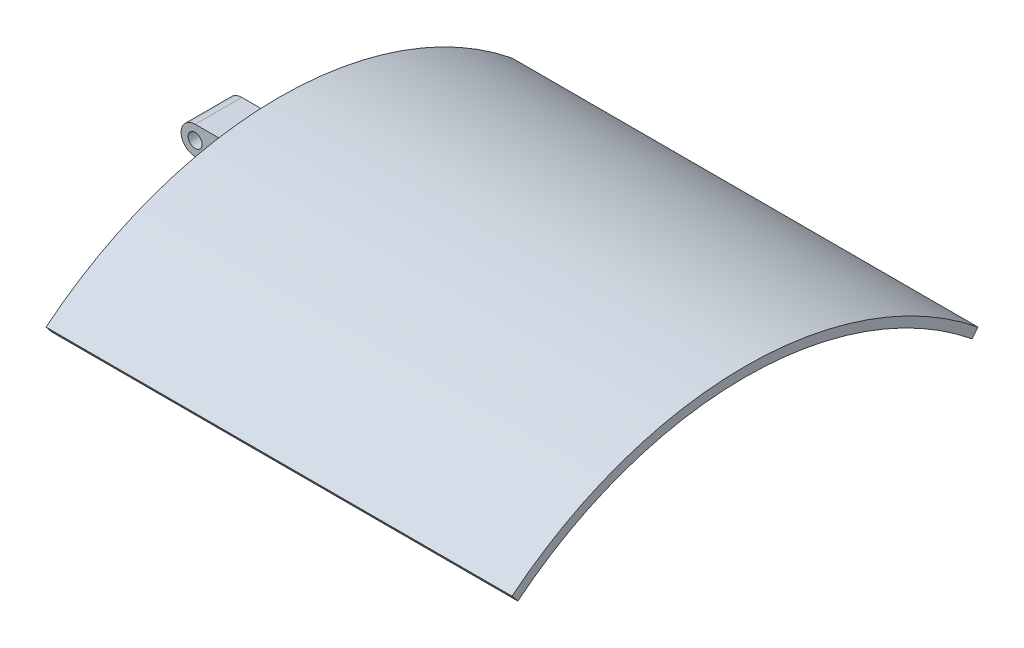
SolidWorks part; units mm, degrees
ref_plane "Plan de face" through (0, 0, 0) normal (0, 0, 1) x (1, 0, 0)
ref_plane "Plan de dessus" through (0, 0, 0) normal (0, 1, 0) x (1, 0, 0)
ref_plane "Plan de droite" through (0, 0, 0) normal (1, 0, 0) x (0, 0, -1)
sketch "Esquisse1" plane through (0, 0, 0) normal (1, 0, 0) x (0, 0, -1)
  line L0 (-50, 61.8082) -> (0, 0) construction
  line L1 (0, 0) -> (50, 61.8082) construction
  line L2 (-50, 61.8082) -> (50, 61.8082) construction
  line L3 (0, 61.8082) -> (0, 0) construction
  line L4 (-50, 61.8082) -> (-48.7421, 60.2532)
  line L5 (50, 61.8082) -> (48.7421, 60.2532)
  arc A0 (-50, 61.8082) -> (50, 61.8082) centre (0, 0) cw
  arc A1 (-48.7421, 60.2532) -> (48.7421, 60.2532) centre (0, 0) cw
  dimension "D1" = 77.5
  dimension "D2" = 77.943
  dimension "D3" = 2
  dimension "D4" = 100
extrude "Boss.-Extru.1" add sketch "Esquisse1" along normal blind 100
sketch "Esquisse7" plane through (0, 0, 0) normal (0, 0, 1) x (1, 0, 0)
  line L0 (7, 77.5) -> (7, 70.5)
  line L1 (100, 77.5) -> (0, 77.5) construction
  line L2 (7, 77.5) -> (13, 77.5)
  line L3 (13, 77.5) -> (13, 64.5)
  line L5 (13, 64.5) -> (-13, 64.5)
  line L6 (-13, 64.5) -> (-13, 70.5) construction
  line L7 (-13, 70.5) -> (7, 70.5)
  line L10 (10, 77.5) -> (0, 77.5) construction
  line L11 (-13, 67.5) -> (7, 67.5) construction
  line L12 (7, 67.5) -> (7, 70.5) construction
  line L13 (7, 67.5) -> (7, 64.5) construction
  line L14 (7, 70.5) -> (-1.6824, 119.7404) construction
  circle A0 centre (-13, 67.5) radius 1.5
  arc A1 (-13, 70.5) -> (-13, 64.5) centre (-13, 67.5) ccw
  dimension "D3" = 3
  dimension "D1" = 6
  dimension "D2" = 10
  dimension "D4" = 23
  dimension "D5" = 10
  dimension "D6" = 80
  dimension "D7" = 50
extrude "Boss.-Extru.3" add sketch "Esquisse7" along normal blind 5 and the other way blind 5 contours L7 L0 L2 L3 L5 A1 | A0
sketch "Esquisse3" plane through (0, 0, 0) normal (0, 0, 1) x (1, 0, 0)
  line L0 (30.7214, 77.5) -> (30.7214, 72.5)
  line L1 (100, 77.5) -> (13, 77.5) construction
  line L2 (30.7214, 72.5) -> (36.7214, 72.5) construction
  line L3 (36.7214, 72.5) -> (36.7214, 77.5)
  line L4 (36.7214, 77.5) -> (30.7214, 77.5)
  line L5 (-74.1468, 29.3655) -> (-127.2256, 20.0063) construction
  line L6 (-73.1207, 23.5464) -> (-132.9596, 12.9952) construction
  line L7 (-11, 40.5) -> (-11, 34.5) construction
  line L8 (-13, 67.5) -> (-11, 67.5) construction
  line L9 (36.7214, -12.0757) -> (36.7214, -21.0592) construction
  line L10 (30.7214, 72.5) -> (36.7214, 72.5) construction
  line L11 (30.7214, -123.9412) -> (30.7214, -122.8027) construction
  line L12 (72.7696, 84.9142) -> (60.2573, 82.708) construction
  line L13 (132.8929, 62.8722) -> (91.2136, 55.523) construction
  line L14 (123.3905, 91.5493) -> (80.4346, 83.975) construction
  line L15 (-13, 67.5) -> (-7.8094, 38.0626) construction
  line L16 (-11, 37.5) -> (-16.5823, 69.1591) construction
  line L17 (-13, 67.5) -> (-11, 37.5) construction
  line L18 (-11, 37.5) -> (33.7214, 77.5) construction
  line L19 (33.7214, 77.5) -> (-13, 67.5) construction
  line L20 (30.7214, 77.5) -> (-13, 77.5) construction
  line L21 (-13, 77.5) -> (-13, 67.5) construction
  line L22 (-11, 67.5) -> (-11, 37.5) construction
  arc A0 (-11, 40.5) -> (-11, 34.5) centre (-11, 37.5) ccw
  circle A1 centre (-11, 37.5) radius 1.5
  arc A2 (-11, 34.5) -> (36.7214, 72.5) centre (-2.2688, 72.5) ccw construction
  arc A3 (-11, 40.5) -> (30.7214, 72.5) centre (-2.4112, 72.5) ccw construction
  spline S0 degree 3 poles (30.7214, 72.5) (30.7214, 44.695) (24.9104, 46.832) (-11, 40.5) knots 0 0 0 0 1 1 1 1
  spline S1 degree 3 poles (36.7214, 72.5) (36.7214, 41.4065) (28.3973, 41.4468) (-11, 34.5) knots 0 0 0 0 1 1 1 1
  text T0 "A"
  text T1 "C"
  text T2 "B"
  text T3 "B'"
  point P18 (0, 0)
  point P27 (-13, 67.5)
  point P34 (44.8238, 93.2878)
  point P35 (37.374, 77.5)
  point P37 (37.8502, 77.5)
  point P39 (-10.5441, 27.444)
  point P40 (-12, 67.5)
  point P41 (-13, 76.0376)
  dimension "D4" = 3
  dimension "D5" = 12.081
  dimension "D1" = 30.0666
  dimension "D2" = 5
  dimension "D3" = 6
  dimension "D6" = 10
  dimension "D7" = 3.2398
  dimension "D8" = 60
  dimension "D9" = 2
  dimension "D10" = 30.0666
  dimension "D11" = 40
extrude "Boss.-Extru.2" add sketch "Esquisse3" along normal blind 3 and the other way blind 3 contours L3 L4 L0 S0 A0 S1 | A1
ref_plane "Plan2" through (0, 67.5, 0) normal (0, 1, 0) x (1, 0, 0)
ref_plane "Plan3" through (0, 0, 0) normal (0, 0, 1) x (1, 0, 0)
ref_plane "Plan4" through (0, 79.5, 0) normal (0, 1, 0) x (1, 0, 0)
sketch "Esquisse8" plane through (0, 79.5, 0) normal (0, 1, 0) x (1, 0, 0)
  line L0 (30.7214, -3) -> (36.7214, -3) construction
  line L1 (30.7214, 3) -> (30.7214, -3) construction
  line L2 (30.7214, 3) -> (36.7214, 3) construction
  line L3 (30.7214, -3) -> (36.7214, -3) construction
  line L4 (30.7214, 3) -> (30.7214, -3) construction
  line L5 (30.7214, 3) -> (36.7214, 3) construction
  line L6 (36.7214, -3) -> (36.7214, 3) construction
  line L7 (36.7214, -3) -> (36.7214, 3) construction
  line L8 (30.7214, -3) -> (36.7214, 3) construction
  line L9 (30.7214, 3) -> (36.7214, -3) construction
  point P3 (33.7214, 0)
  point P5 (0, 0)
sketch "Esquisse9" plane through (0, 0, 0) normal (0, 0, 1) x (1, 0, 0)
  line L0 (-11, 37.5) -> (-13, 67.5) construction
  line L1 (-13, 67.5) -> (33.7214, 79.5) construction
  line L2 (33.7214, 79.5) -> (-11, 37.5) construction
  line L3 (100, 79.5) -> (0, 79.5) construction
  line L4 (100, 79.5) -> (0, 79.5) construction
  line L5 (-13, 67.5) -> (-13, 79.5) construction
  line L6 (-13, 79.5) -> (0, 79.5) construction
  point P0 (-13, 67.5)
  point P1 (-11, 37.5)
  dimension "D1" = 50.611
  dimension "D2" = 28.798
  dimension "D3" = 100.591
  dimension "D4" = 14.405
